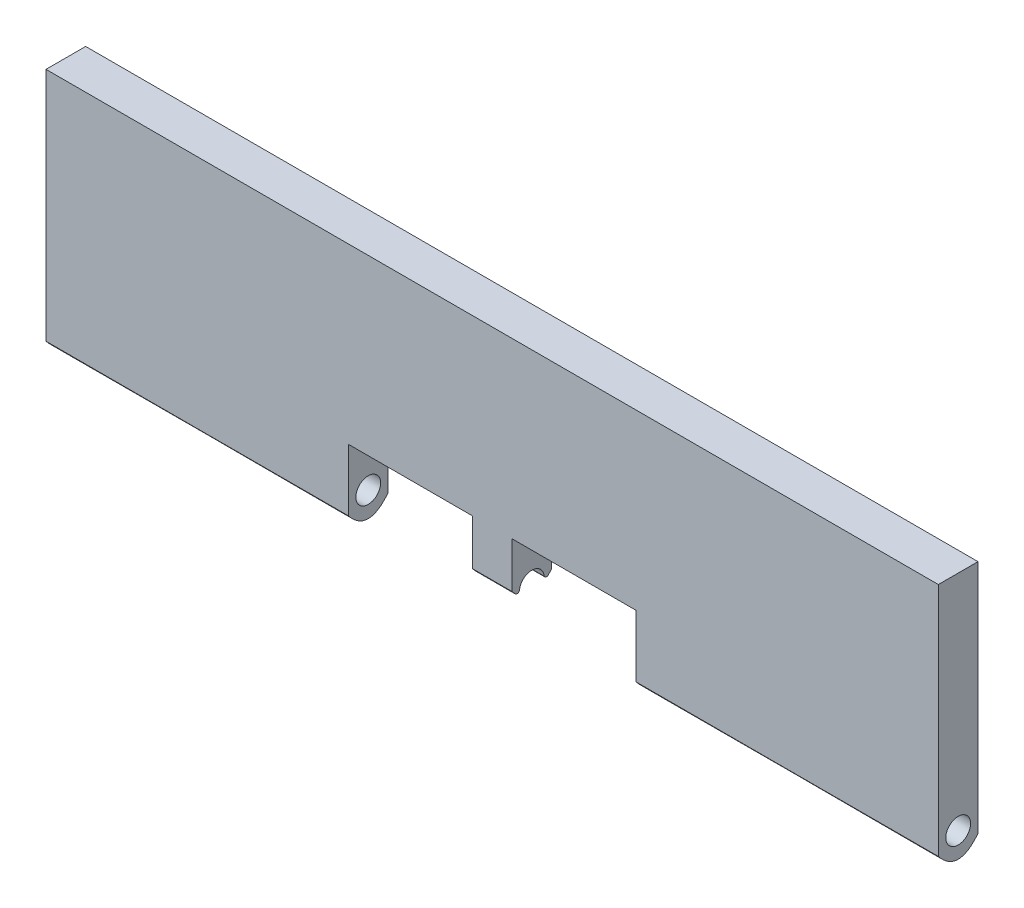
SolidWorks part; units mm, degrees
ref_plane "Plan de face" through (0, 0, 0) normal (0, 0, 1) x (1, 0, 0)
ref_plane "Plan de dessus" through (0, 0, 0) normal (0, 1, 0) x (1, 0, 0)
ref_plane "Plan de droite" through (0, 0, 0) normal (1, 0, 0) x (0, 0, -1)
sketch "Esquisse1" plane through (0, 0, 0) normal (0, 0, 1) x (1, 0, 0)
  line L0 (-29, -25) -> (-29, -10)
  line L1 (-90, -25) -> (-29, -25)
  line L2 (-90, -25) -> (-90, 25)
  line L3 (-90, 25) -> (90, 25)
  line L4 (90, -25) -> (90, 25)
  line L5 (-90, -25) -> (90, 25) construction
  line L6 (-90, 25) -> (90, -25) construction
  line L7 (-29, -10) -> (-4, -10)
  line L8 (-4, -10) -> (-4, -25)
  line L9 (0, 0) -> (0, -25) construction
  line L10 (-4, -25) -> (4, -25)
  line L11 (4, -10) -> (4, -25)
  line L12 (29, -10) -> (4, -10)
  line L13 (29, -25) -> (29, -10)
  line L14 (29, -25) -> (90, -25)
  point P0 (0, 0)
  dimension "D1" = 180
  dimension "D2" = 50
  dimension "D3" = 25
  dimension "D4" = 4
  dimension "D5" = 15
extrude "Boss.-Extru.1" add sketch "Esquisse1" along normal blind 8
sketch "Esquisse2" plane through (-90, 0, 0) normal (-1, 0, 0) x (0, 0, 1)
  line L0 (4, -25) -> (4, -8.5674) construction
  line L1 (8, -25) -> (0, -25) construction
  line L2 (4, -22.5) -> (0, -22.5) construction
  line L3 (0, 25) -> (0, -25) construction
  line L4 (8, 25) -> (8, -25) construction
  line L5 (0, -22.5) -> (0, -25)
  line L6 (0, -25) -> (8, -25)
  line L7 (8, -25) -> (8, -22.5)
  circle A0 centre (4, -20) radius 2.5
  spline S0 degree 2 poles (0, -22.5) (4, -27.5) (8, -22.5) knots 0 0 0 1 1 1
  line M1 (0, 25) -> (0, -25)
  line M2 (0, -25) -> (8, -25)
  line M3 (8, -25) -> (8, 25)
  dimension "D1" = 5
  dimension "D2" = 5
extrude "Enlèv. mat.-Extru.1" cut sketch "Esquisse2" against normal up to surface (180 mm away) contours S0 L6 M3 | S0 M1 M2 | A0 region at (-90, -24.25, 1) region at (-90, -24.25, 7) region at (-90, -20, 4) up to face at (90, 0, 4)
sketch "Esquisse4" plane through (0, 0, 0) normal (1, 0, 0) x (0, 0, -1)
  line L0 (0, 0) -> (6, 0) construction
  line L1 (6, 6) -> (0, 6)
  line L2 (0, 25) -> (0, -22.5) construction
  line L3 (6, -6) -> (0, -6)
  line L4 (0, 6) -> (0, -6)
  arc A1 (6, -6) -> (6, 6) centre (6, 0) ccw
  dimension "D3" = 6
extrude "Boss.-Extru.2" add sketch "Esquisse4" along normal blind 2.5 and the other way blind 2.5
sketch "Esquisse6" plane through (-4, 0, 0) normal (-1, 0, 0) x (0, 0, 1)
  line L0 (1.6529, -20.8608) -> (6.3471, -20.8608) construction
  line L1 (8, -19.2216) -> (8, -22.5)
  line L2 (0, -19.2216) -> (0, -22.5)
  parabola Q0 (8, -22.5) -> (0, -22.5) focus (4, -23.4) apex (4, -25) construction
  parabola Q1 (0, -22.5) -> (8, -22.5) focus (4, -23.4) apex (4, -25) construction
  spline S1 degree 2 poles (0, -22.5) (4, -27.5) (8, -22.5) knots 0 0 0 1 1 1
  spline S2 degree 2 poles (0, -19.2216) (4, -24.2216) (8, -19.2216) knots 0 0 0 1 1 1
  point P0 (4, -20)
  point P19 (6.3471, -20.8608)
  point P20 (1.6529, -20.8608)
extrude "Enlèv. mat.-Extru.2" cut sketch "Esquisse6" against normal up to surface (8 mm away) up to face at (4, -22.5, 4)
fillet "Congé1" radius 0.5 2 edges at (0, -20.8608, 1.6529) (0, -20.8608, 6.3471)
